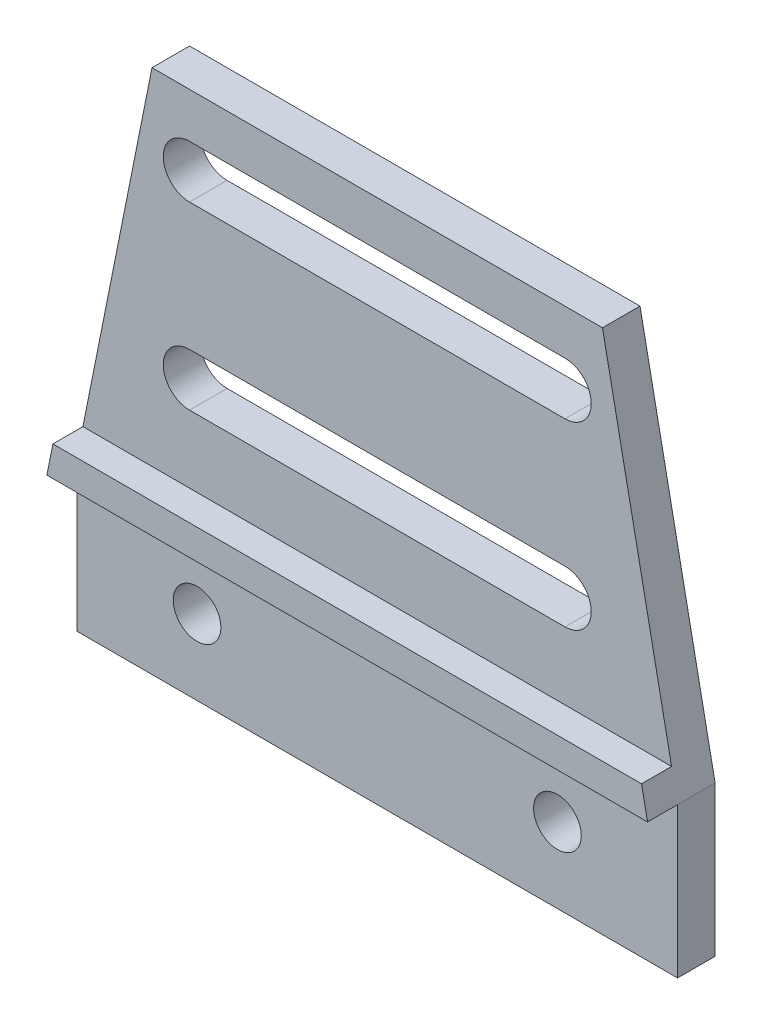
SolidWorks part; units mm, degrees
ref_plane "Alzado" through (0, 0, 0) normal (0, 0, 1) x (1, 0, 0)
ref_plane "Planta" through (0, 0, 0) normal (0, 1, 0) x (1, 0, 0)
ref_plane "Vista lateral" through (0, 0, 0) normal (1, 0, 0) x (0, 0, -1)
sketch "Croquis1" plane through (0, 0, 0) normal (0, 0, 1) x (1, 0, 0)
  line L0 (0, 5) -> (0, -5) construction
  line L1 (-20, -5) -> (20, -5)
  line L2 (-20, -5) -> (-20, 5)
  line L3 (-20, 5) -> (20, 5)
  line L4 (20, -5) -> (20, 5)
  line L5 (-20, -5) -> (20, 5) construction
  line L6 (-20, 5) -> (20, -5) construction
  line L7 (15, 30) -> (-15, 30)
  line L8 (0, 30) -> (0, 5)
  line L9 (-20, 5) -> (20, 5)
  line L10 (-15, 30) -> (-20, 5)
  line L11 (15, 30) -> (20, 5)
  arc A0 (-20, 5) -> (-15, 30) centre (-32.6118, 20.5224) ccw construction
  arc A1 (20, 5) -> (15, 30) centre (32.6118, 20.5224) cw construction
  point P0 (0, 0)
  dimension "D4" = 20
  dimension "D1" = 10
  dimension "D2" = 40
  dimension "D3" = 15
  dimension "D5" = 25
extrude "Saliente-Extruir1" add sketch "Croquis1" along normal blind 2.5 contours L1 L4 L3 L2 | L10 L3 L8 L7 | L3 A1 L7 L8 region at (0, 0, 0) region at (-8.8095, 16.9048, 0) region at (8.8095, 16.9048, 0)
sketch "Croquis2" plane through (0, 0, 2.5) normal (0, 0, 1) x (1, 0, 0)
  line L0 (-20, 5) -> (20, 5) construction
  line L1 (-20, 5) -> (20, 5)
  line L2 (-19.6, 7) -> (19.6, 7)
  line L6 (-20, -5) -> (20, -5)
  line L7 (20, -5) -> (20, 5)
  line L8 (15, 30) -> (-15, 30)
  line L9 (-20, 5) -> (-20, -5)
  line L10 (-20, -5) -> (20, -5)
  line L11 (20, -5) -> (20, 5)
  line L12 (15, 30) -> (-15, 30)
  line L13 (-20, 5) -> (-20, -5)
  line L16 (-15, 30) -> (-20, 5)
  line L17 (-15, 30) -> (-20, 5)
  line L19 (20, 5) -> (15, 30)
  line L20 (20, 5) -> (15, 30)
  point P6 (0, 0)
  point P10 (0, 0)
  line M13 (-15, 30) -> (-20, 5)
  dimension "D2" = 2
  dimension "D1" = 0
extrude "Saliente-Extruir2" add sketch "Croquis2" along normal blind 2 contours L2 L1 M13 region at (0, 5.9966, 2.5)
sketch "Croquis3" plane through (0, 0, 2.5) normal (0, 0, 1) x (1, 0, 0)
  line L0 (0, 0) -> (-12, 0) construction
  line L1 (0, -7.8912) -> (0, 8.2069) construction
  circle A0 centre (-12, 0) radius 1.5875
  circle A1 centre (12, 0) radius 1.5875
  dimension "D1" = 3.175
  dimension "D2" = 12
extrude "Cortar-Extruir1" cut sketch "Croquis3" against normal blind 12
sketch "Croquis4" plane through (0, 0, 2.5) normal (0, 0, 1) x (1, 0, 0)
  line L0 (0, -5) -> (0, 30) construction
  line L1 (15, 30) -> (-15, 30) construction
  line L2 (-20, -5) -> (20, -5) construction
  line L3 (-12.5, 25.25) -> (12.5, 25.25) construction
  line L4 (-12.5, 27) -> (12.5, 27)
  line L5 (-12.5, 23.5) -> (12.5, 23.5)
  line L6 (32.6172, 19.25) -> (-26.2091, 19.25) construction
  line L7 (-12.5, 13.25) -> (12.5, 13.25) construction
  line L8 (-12.5, 11.5) -> (12.5, 11.5)
  line L9 (-12.5, 15) -> (12.5, 15)
  arc A0 (-12.5, 27) -> (-12.5, 23.5) centre (-12.5, 25.25) ccw
  arc A1 (12.5, 23.5) -> (12.5, 27) centre (12.5, 25.25) ccw
  arc A2 (-12.5, 11.5) -> (-12.5, 15) centre (-12.5, 13.25) cw
  arc A3 (12.5, 15) -> (12.5, 11.5) centre (12.5, 13.25) cw
  point P9 (0, 25.25)
  point P18 (0, 13.25)
  dimension "D1" = 3.5
  dimension "D2" = 25
  dimension "D3" = 3
  dimension "D4" = 6
extrude "Cortar-Extruir2" cut sketch "Croquis4" against normal blind 12
